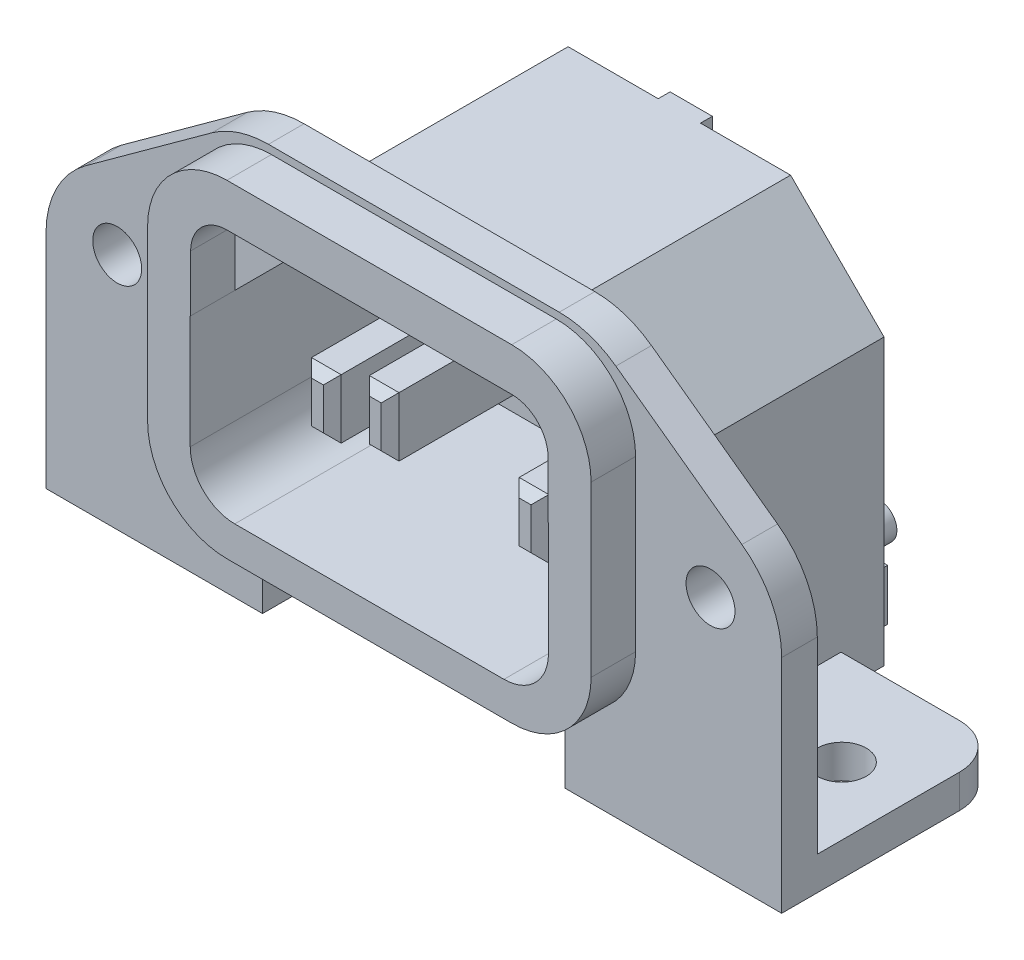
SolidWorks part; units mm, degrees
ref_plane "Front Plane" through (0, 0, 0) normal (0, 0, 1) x (1, 0, 0)
ref_plane "Top Plane" through (0, 0, 0) normal (0, 1, 0) x (1, 0, 0)
ref_plane "Right Plane" through (0, 0, 0) normal (1, 0, 0) x (0, 0, -1)
sketch "Sketch1" plane through (0, 0, 0) normal (0, 0, 1) x (1, 0, 0)
  line L0 (-22.1179, 6.3931) -> (-13.6201, 12.5605)
  line L1 (-9.8022, 13.8) -> (9.8022, 13.8)
  line L2 (-24.8, 1.1326) -> (-24.8, -13.8)
  line L3 (-24.8, -13.8) -> (-10.15, -13.8)
  line L4 (24.8, 1.1326) -> (24.8, -13.8)
  line L5 (-24.8, 13.8) -> (24.8, -13.8) construction
  line L6 (-24.8, -13.8) -> (17.5053, 9.7408) construction
  line L7 (0, 0) -> (0, 18.0303) construction
  line L8 (22.1179, 6.3931) -> (13.6201, 12.5605)
  line L9 (9.8022, 13.8) -> (24.8, 13.8) construction
  line L10 (17.5053, 9.7408) -> (24.8, 13.8) construction
  line L11 (24.8, 13.8) -> (24.8, 1.1326) construction
  line L12 (-20, 0.6) -> (-11.571, 0.6) construction
  line L13 (-21.65, 2.25) -> (-21.65, -1.1534) construction
  line L14 (-10.15, -13.8) -> (-10.15, -10.05)
  line L15 (-10.15, -10.05) -> (10.15, -10.05)
  line L16 (10.15, -10.05) -> (10.15, -13.8)
  line L17 (-10.15, -13.8) -> (10.15, -13.8) construction
  line L18 (10.15, -13.8) -> (24.8, -13.8)
  line L19 (-9.6, 13.3) -> (9.6, 13.3)
  line L20 (-9.6, 10.45) -> (9.6, 10.45) construction
  line L21 (-12.1, 7.95) -> (-12.1, -3.45) construction
  line L22 (-9.6, -5.95) -> (9.6, -5.95) construction
  line L23 (12.1, 7.95) -> (12.1, -3.45) construction
  line L24 (-12.1, 10.45) -> (12.1, -5.95) construction
  line L25 (-12.1, -5.95) -> (12.1, 10.45) construction
  line L26 (14.95, 7.95) -> (14.95, -3.45)
  line L27 (-9.6, -8.8) -> (9.6, -8.8)
  line L28 (-14.95, 7.95) -> (-14.95, -3.45)
  line L29 (-12.05, 7.95) -> (-12.05, -3.45)
  line L30 (-9.6, -5.9) -> (9.6, -5.9)
  line L31 (12.05, 7.95) -> (12.05, -3.45)
  line L32 (-9.6, 10.4) -> (9.6, 10.4)
  arc A0 (-9.8022, 13.8) -> (-13.6201, 12.5605) centre (-9.8022, 7.3) ccw
  arc A1 (-24.8, 1.1326) -> (-22.1179, 6.3931) centre (-18.3, 1.1326) cw
  arc A2 (24.8, 1.1326) -> (22.1179, 6.3931) centre (18.3, 1.1326) ccw
  arc A3 (9.8022, 13.8) -> (13.6201, 12.5605) centre (9.8022, 7.3) cw
  circle A4 centre (-20, 2.25) radius 1.65
  circle A5 centre (20, 2.25) radius 1.65
  arc A6 (-12.1, -3.45) -> (-9.6, -5.95) centre (-9.6, -3.45) ccw construction
  arc A7 (12.1, -3.45) -> (9.6, -5.95) centre (9.6, -3.45) cw construction
  arc A8 (12.1, 7.95) -> (9.6, 10.45) centre (9.6, 7.95) ccw construction
  arc A9 (-12.1, 7.95) -> (-9.6, 10.45) centre (-9.6, 7.95) cw construction
  arc A10 (14.95, 7.95) -> (9.6, 13.3) centre (9.6, 7.95) ccw
  arc A11 (14.95, -3.45) -> (9.6, -8.8) centre (9.6, -3.45) cw
  arc A12 (-14.95, -3.45) -> (-9.6, -8.8) centre (-9.6, -3.45) ccw
  arc A13 (-14.95, 7.95) -> (-9.6, 13.3) centre (-9.6, 7.95) cw
  arc A14 (-12.05, -3.45) -> (-9.6, -5.9) centre (-9.6, -3.45) ccw
  arc A15 (12.05, -3.45) -> (9.6, -5.9) centre (9.6, -3.45) cw
  arc A16 (12.05, 7.95) -> (9.6, 10.4) centre (9.6, 7.95) ccw
  arc A17 (-12.05, 7.95) -> (-9.6, 10.4) centre (-9.6, 7.95) cw
  point P0 (0, 0)
  point P32 (0, -10.05)
  point P34 (0, 2.25)
  point P39 (0, 0)
  point P40 (0, 0)
  dimension "D5" = 251.942
  dimension "D1" = 6.5
  dimension "D6" = 3.3
  dimension "D13" = 2.5
  dimension "D2" = 49.6
  dimension "D3" = 27.6
  dimension "D4" = 10.5
  dimension "D7" = 14.4
  dimension "D8" = 3.15
  dimension "D9" = 3.75
  dimension "D10" = 20.3
  dimension "D11" = 16.4
  dimension "D12" = 24.2
  dimension "D14" = 2.85
  dimension "D15" = 0.05
extrude "Boss-Extrude1" add sketch "Sketch1" along normal blind 2.4 contours A3 L1 A0 L0 A1 L2 L3 L14 L15 L16 L18 L4 A2 L8 A5 A4 L28 A13 L19 A10 L26 A11 L27 A12 | A13 L28 A12 L27 A11 L26 A10 L19 L21 A9 L20 A8 L23 A7 L22 A6 region at (-17.5356, 9.0174, 0) region at (0, 12.9282, 0)
extrude "Boss-Extrude2" add sketch "Sketch1<3>" along normal blind 3 from surface contours A13 L28 A12 L27 A11 L26 A10 L19 L21 A9 L20 A8 L23 A7 L22 A6 region at (0, 12.9282, 0) starting at face at (21.65, 2.25, 2.4)
sketch "Sketch1<3>" plane through (0, 0, 0) normal (0, 0, 1) x (1, 0, 0) same geometry as "Sketch1"
sketch "Sketch2" plane through (0, 0, 0) normal (0, 0, -1) x (-1, 0, 0)
  line L0 (24.8, -13.8) -> (10.15, -13.8) construction
  line L1 (-7.5, 11.7) -> (7.5, 11.7)
  line L2 (-13.8, 5.4) -> (-13.8, -13.8)
  line L3 (-13.8, -13.8) -> (13.8, -13.8)
  line L4 (13.8, 5.4) -> (13.8, -13.8)
  line L5 (-10.5254, 8.6746) -> (13.8, -13.8) construction
  line L6 (-13.8, -13.8) -> (10.5254, 8.6746) construction
  line L7 (-13.8, 5.4) -> (-7.5, 11.7)
  line L8 (7.5, 11.7) -> (13.8, 5.4)
  line L9 (0, -1.05) -> (0, 19.8116) construction
  line L10 (-13.8, 11.7) -> (-7.5, 11.7) construction
  line L11 (-13.8, 11.7) -> (-10.5254, 8.6746) construction
  line L12 (-13.8, 11.7) -> (-13.8, 5.4) construction
  line L13 (7.5, 11.7) -> (13.8, 11.7) construction
  line L14 (10.5254, 8.6746) -> (13.8, 11.7) construction
  line L15 (13.8, 11.7) -> (13.8, 5.4) construction
  point P0 (0, -1.05)
  point P14 (0, 0)
  dimension "D1" = 25.5
  dimension "D2" = 15
  dimension "D3" = 6.3
  dimension "D4" = 90
extrude "Boss-Extrude3" add sketch "Sketch2" along normal blind 15.5 and the other way offset from surface 3 other way up to face at (0, 2.25, 5.4)
sketch "Sketch3" plane through (0, 0, 2.4) normal (0, 0, 1) x (1, 0, 0)
  line L0 (-12.05, 7.15) -> (-8.8, 10.4)
  line L1 (0, 0) -> (0, 16.9382) construction
  line L2 (12.05, 7.15) -> (8.8, 10.4)
  arc A1 (-12.05, 7.15) -> (-8.8, 10.4) centre (-9.7647, 8.1147) cw
  arc A2 (12.05, 7.15) -> (8.8, 10.4) centre (9.7647, 8.1147) ccw
  point P11 (0, 0)
  point P12 (0, 0)
  point P13 (-8.8, 10.4)
  point P15 (0, 0)
  point P16 (-12.05, 7.15)
sketch "Sketch4" plane through (0, 0, -15.5) normal (0, 0, -1) x (-1, 0, 0)
  line L0 (12.075, -3.5) -> (12.075, 4.131)
  line L1 (12.075, 4.131) -> (6.206, 10)
  line L2 (6.206, 10) -> (-6.206, 10)
  line L3 (-6.206, 10) -> (-12.075, 4.131)
  line L4 (-12.075, 4.131) -> (-12.075, -3.5)
  line L5 (-9.075, -6.5) -> (9.075, -6.5)
  line L6 (13.8, -13.8) -> (13.8, 5.4)
  line L7 (13.8, 5.4) -> (7.5, 11.7)
  line L8 (7.5, 11.7) -> (-7.5, 11.7)
  line L9 (-7.5, 11.7) -> (-13.8, 5.4)
  line L10 (-13.8, 5.4) -> (-13.8, -13.8)
  line L11 (-13.8, -13.8) -> (13.8, -13.8)
  line L12 (13.8, -13.8) -> (13.8, 5.4) construction
  line L13 (13.8, 5.4) -> (7.5, 11.7) construction
  line L14 (7.5, 11.7) -> (-7.5, 11.7) construction
  line L15 (-7.5, 11.7) -> (-13.8, 5.4) construction
  line L16 (-13.8, 5.4) -> (-13.8, -13.8) construction
  line L17 (-13.8, -13.8) -> (13.8, -13.8) construction
  line L19 (0, 0) -> (0, 16.9382) construction
  arc A0 (12.075, -3.5) -> (9.075, -6.5) centre (9.075, -3.5) cw
  arc A1 (-9.075, -6.5) -> (-12.075, -3.5) centre (-9.075, -3.5) cw
  dimension "D6" = 3
  dimension "D3" = 24.15
  dimension "D2" = 16.5
  dimension "D4" = 8.3
  dimension "D5" = 270
  dimension "D1" = 0
extrude "Cut-Extrude1" cut sketch "Sketch4" against normal blind 25.5 from offset 5 offset against normal yes
extrude "Boss-Extrude4" add sketch "Sketch3" against normal up to surface (2.4 mm away) up to face at (21.65, 2.25, 0)
sketch "Sketch6" plane through (0, -13.8, 0) normal (0, -1, 0) x (1, 0, 0)
  line L0 (-24.8, 0) -> (-24.8, -9.6)
  line L1 (-21.8, -12.6) -> (-13.8, -12.6)
  line L2 (-13.8, 0) -> (-13.8, -15.5) construction
  line L3 (-24.8, 2.4) -> (24.8, 2.4) construction
  line L4 (-24.8, 0) -> (-13.8, 0)
  line L5 (-13.8, 0) -> (-13.8, -12.6)
  line L6 (-21.9, -6.2) -> (-21.9, -4.6864) construction
  line L7 (-20.25, -7.85) -> (-18.4114, -7.85) construction
  line L8 (0, 0) -> (0, -9.1869) construction
  line L9 (24.8, 0) -> (13.8, 0)
  line L10 (24.8, 0) -> (24.8, -9.6)
  line L11 (21.8, -12.6) -> (13.8, -12.6)
  line L12 (13.8, 0) -> (13.8, -12.6)
  arc A0 (-24.8, -9.6) -> (-21.8, -12.6) centre (-21.8, -9.6) ccw
  circle A1 centre (-20.25, -6.2) radius 1.65
  circle A2 centre (20.25, -6.2) radius 1.65
  arc A3 (24.8, -9.6) -> (21.8, -12.6) centre (21.8, -9.6) cw
  dimension "D1" = 15
  dimension "D2" = 3
  dimension "D3" = 2.9
  dimension "D5" = 3.3
  dimension "D4" = 4.75
extrude "Boss-Extrude5" add sketch "Sketch6" against normal blind 2.25
sketch "Sketch7" plane through (0, 0, 2.4) normal (0, 0, 1) x (1, 0, 0)
  line L0 (-10.2, -13.8) -> (-10.2, -9.8)
  line L1 (-24.8, -13.8) -> (24.8, -13.8) construction
  line L2 (-10.2, -9.8) -> (10.2, -9.8)
  line L3 (10.2, -9.8) -> (10.2, -13.8)
  line L4 (0, 0) -> (0, -4.0727) construction
  line L5 (-10.2, -13.8) -> (10.2, -13.8)
  dimension "D1" = 4
  dimension "D2" = 20.4
extrude "Cut-Extrude2" cut sketch "Sketch7" against normal blind 16
sketch "Sketch8" plane through (0, 0, -15.5) normal (0, 0, -1) x (-1, 0, 0)
  line L0 (0, 16.86) -> (0, -19.181) construction
  line L1 (-1.425, 11.7) -> (-1.425, 6.3)
  line L2 (-7.5, 11.7) -> (7.5, 11.7) construction
  line L3 (-2.6476, 3.3324) -> (-1.3, -2.2)
  line L4 (-1.3, -2.2) -> (-1.3, -10.1)
  line L5 (-13.8, -13.8) -> (13.8, -13.8) construction
  line L6 (-1.3, -10.1) -> (-0.65, -14.85)
  line L7 (-0.65, -14.85) -> (-0.65, -17.85)
  line L8 (-2.725, 3.9773) -> (2.725, 3.9773) construction
  line L9 (-0.65, -17.85) -> (0.65, -17.85)
  line L10 (-1.425, 11.7) -> (1.425, 11.7)
  line L11 (7.5, 11.7) -> (-7.5, 11.7) construction
  line L12 (0.65, -14.85) -> (0.65, -17.85)
  line L13 (-0.75, 10.2) -> (0.75, 10.2)
  line L14 (-0.75, 10.2) -> (-0.75, 7.2)
  line L15 (-0.75, 7.2) -> (0.75, 7.2)
  line L16 (0.75, 10.2) -> (0.75, 7.2)
  line L17 (-0.75, 10.2) -> (0.75, 7.2) construction
  line L18 (-0.75, 7.2) -> (0.75, 10.2) construction
  line L19 (1.3, -10.1) -> (0.65, -14.85)
  line L20 (1.3, -2.2) -> (1.3, -10.1)
  line L21 (2.6476, 3.3324) -> (1.3, -2.2)
  line L22 (1.425, 11.7) -> (1.425, 6.3)
  line L23 (-13.8, -11.55) -> (-13.8, 5.4) construction
  line L24 (4.447, -1.1452) -> (6.9, -4.55)
  line L25 (9.7, 0.55) -> (9.7, -4.55)
  line L26 (6.8, 3.45) -> (12.1154, 3.45) construction
  line L27 (6.9, -4.55) -> (6.9, -9.55)
  line L28 (9.7, -4.55) -> (9.7, -9.55)
  line L29 (6.9, -9.55) -> (8.4, -12.35)
  line L30 (8.4, -12.35) -> (8.4, -17.85)
  line L31 (9.7, -9.55) -> (9.7, -12.35)
  line L32 (9.7, -12.35) -> (9.7, -17.85)
  line L33 (8.4, -17.85) -> (9.7, -17.85)
  line L34 (-9.7, 0.55) -> (-9.7, -4.55)
  line L35 (-9.7, -4.55) -> (-9.7, -9.55)
  line L36 (-9.7, -9.55) -> (-9.7, -12.35)
  line L37 (-9.7, -12.35) -> (-9.7, -17.85)
  line L38 (-8.4, -17.85) -> (-9.7, -17.85)
  line L39 (-8.4, -12.35) -> (-8.4, -17.85)
  line L40 (-6.9, -9.55) -> (-8.4, -12.35)
  line L41 (-6.9, -4.55) -> (-6.9, -9.55)
  line L42 (-4.447, -1.1452) -> (-6.9, -4.55)
  arc A0 (-1.425, 6.3) -> (-2.6476, 3.3324) centre (0, 3.9773) ccw
  circle A1 centre (0, 3.9773) radius 1.25
  arc A2 (1.425, 6.3) -> (2.6476, 3.3324) centre (0, 3.9773) cw
  circle A3 centre (-6.8, 0.55) radius 1.25
  circle A4 centre (6.8, 0.55) radius 1.25
  arc A5 (9.7, 0.55) -> (4.447, -1.1452) centre (6.8, 0.55) ccw
  circle A6 centre (-6.8, 0.55) radius 2.9 construction
  arc A7 (4.447, -1.1452) -> (9.7, 0.55) centre (6.8, 0.55) ccw construction
  arc A8 (-9.7, 0.55) -> (-4.447, -1.1452) centre (-6.8, 0.55) cw
  point P19 (0, 8.7)
  point P28 (0, -17.85)
  point P34 (0, 11.7)
  dimension "D1" = 2.85
  dimension "D9" = 2.5
  dimension "D16" = 13.6
  dimension "D18" = 2.5
  dimension "D19" = 5.8
  dimension "D2" = 5.45
  dimension "D3" = 8.5
  dimension "D4" = 5.4
  dimension "D5" = 2.6
  dimension "D6" = 3.7
  dimension "D7" = 29.55
  dimension "D8" = 3
  dimension "D10" = 3
  dimension "D11" = 1.5
  dimension "D12" = 1.5
  dimension "D13" = 1.3
  dimension "D14" = 7.7227
  dimension "D15" = 13.8
  dimension "D17" = 11.15
  dimension "D20" = 8
  dimension "D21" = 2.8
  dimension "D22" = 5
  dimension "D23" = 2.8
  dimension "D24" = 1.3
extrude "Boss-Extrude6" add sketch "Sketch8" along normal blind 0.8
sketch "Sketch9" plane through (0, 0, -15.5) normal (0, 0, -1) x (-1, 0, 0)
  line L0 (-4.9768, 5.9229) -> (-2.9179, -2.5299)
  line L1 (-2.9179, -2.5299) -> (-2.9179, -7.6)
  line L2 (-8.4, -13.8) -> (-0.7937, -13.8) construction
  line L3 (-2.9179, -13.8) -> (-1.4179, -13.8)
  line L4 (-1.4179, -13.8) -> (-1.4179, -8.4)
  line L5 (-1.4179, -2.3499) -> (-3.5195, 6.2779)
  line L6 (-3.5195, 6.2779) -> (-4.9768, 5.9229)
  line L7 (-2.6476, 3.3324) -> (-1.3, -2.2) construction
  line L8 (0, 0) -> (0, 3.9773) construction
  line L9 (1.4179, -2.3499) -> (3.5195, 6.2779)
  line L10 (1.4179, -13.8) -> (1.4179, -8.4)
  line L11 (2.9179, -13.8) -> (1.4179, -13.8)
  line L12 (2.9179, -2.5299) -> (2.9179, -7.6)
  line L13 (4.9768, 5.9229) -> (2.9179, -2.5299)
  line L14 (3.5195, 6.2779) -> (4.9768, 5.9229)
  line L15 (0.7937, -13.8) -> (8.4, -13.8) construction
  line L16 (1.4179, -4.4057) -> (2.9179, -4.4057) construction
  line L18 (1.4179, -8.4) -> (1.4179, -7.6) construction
  line L19 (1.4179, -7.6) -> (1.4179, -2.3499)
  line L20 (2.9179, -7.6) -> (2.9179, -8.4) construction
  line L21 (2.9179, -8.4) -> (2.9179, -13.8)
  line L22 (-1.4179, -8.4) -> (-1.4179, -7.6) construction
  line L23 (-1.4179, -7.6) -> (-1.4179, -2.3499)
  line L24 (-2.9179, -7.6) -> (-2.9179, -8.4) construction
  line L25 (-2.9179, -8.4) -> (-2.9179, -13.8)
  line L28 (9.7, -17.85) -> (9.7, 0.55) construction
  line L30 (9.7, -13.8) -> (11.5, -13.8)
  line L31 (9.7, -13.8) -> (13.8, -13.8) construction
  line L32 (11.5, -13.8) -> (11.5, -10.35)
  line L33 (11.5, -10.35) -> (9.7, -10.35)
  line L34 (9.7, -10.35) -> (9.7, -13.8)
  line L35 (-11.5, -10.35) -> (-9.7, -10.35)
  line L36 (-11.5, -13.8) -> (-11.5, -10.35)
  line L37 (-9.7, -13.8) -> (-11.5, -13.8)
  line L38 (-9.7, -10.35) -> (-9.7, -13.8)
  arc A0 (2.9179, -8.4) -> (2.9179, -7.6) centre (2.1679, -8) ccw
  arc A1 (1.4179, -8.4) -> (2.9179, -8.4) centre (2.1679, -8) ccw construction
  arc A2 (2.9179, -7.6) -> (1.4179, -7.6) centre (2.1679, -8) ccw construction
  arc A3 (1.4179, -7.6) -> (1.4179, -8.4) centre (2.1679, -8) ccw
  arc A4 (-2.9179, -8.4) -> (-2.9179, -7.6) centre (-2.1679, -8) cw
  arc A5 (-1.4179, -7.6) -> (-1.4179, -8.4) centre (-2.1679, -8) cw
  circle A6 centre (5.675, -8) radius 1.2
  circle A7 centre (10.925, -8) radius 1.2
  circle A8 centre (-10.925, -8) radius 1.2
  circle A9 centre (-5.675, -8) radius 1.2
  point P46 (2.1679, -4.4057)
  dimension "D6" = 5.8
  dimension "D7" = 0.85
  dimension "D8" = 2.4
  dimension "D12" = 2.4
  dimension "D1" = 0.15
  dimension "D2" = 1.5
  dimension "D3" = 1.5
  dimension "D4" = 11.4501
  dimension "D5" = 8.7
  dimension "D9" = 1.8
  dimension "D10" = 3.45
  dimension "D11" = 5.675
  dimension "D13" = 5.25
extrude "Boss-Extrude10" add sketch "Sketch9" along normal blind 2.54
sketch "Sketch10" plane through (0, 0, -13.6) normal (0, 0, 1) x (1, 0, 0)
  line L0 (0, 0) -> (0, -20.0579) construction
  line L1 (8.6, -13.8) -> (8.6, -11.1)
  line L2 (-10.2, -13.8) -> (10.2, -13.8) construction
  line L3 (8.6, -11.1) -> (5.9, -11.1)
  line L4 (5.9, -11.1) -> (5.9, -13.8)
  line L5 (1.65, -13.8) -> (1.65, -11.1)
  line L6 (1.65, -11.1) -> (-1.65, -11.1)
  line L7 (-1.65, -11.1) -> (-1.65, -13.8)
  line L8 (10.2, -13.8) -> (10.2, -9.8) construction
  line L9 (5.9, -13.8) -> (8.6, -13.8)
  line L10 (1.65, -13.8) -> (-1.65, -13.8)
  line L11 (-5.9, -11.1) -> (-5.9, -13.8)
  line L12 (-8.6, -11.1) -> (-5.9, -11.1)
  line L13 (-8.6, -13.8) -> (-8.6, -11.1)
  line L14 (-5.9, -13.8) -> (-8.6, -13.8)
  point P11 (0, -11.1)
  dimension "D1" = 1.6
  dimension "D2" = 2.7
  dimension "D3" = 3.3
  dimension "D4" = 2.7
extrude "Cut-Extrude3" cut sketch "Sketch10" against normal up to surface (1.9 mm away) up to face at (-9.05, -15.825, -15.5)
sketch "Sketch11" plane through (0, 0, -15.5) normal (0, 0, -1) x (-1, 0, 0)
  line L0 (-12.1, -5.55) -> (-10.1973, -5.55) construction
  line L1 (0, 0) -> (0, -4.9949) construction
  line L2 (12.1, -5.55) -> (10.1973, -5.55) construction
  line L3 (-10.925, -6.8) -> (-12.9823, -6.8) construction
  line L4 (-13.8, -11.55) -> (-13.8, 5.4) construction
  circle A0 centre (-10.925, -8) radius 1.2 construction
  circle A1 centre (-10.925, -8) radius 1.2 construction
  text T0 "N" font "Century Gothic" height 2
  text T1 "L" font "Century Gothic" height 2
  dimension "D1" = 1.25
  dimension "D2" = 1.7
extrude "Boss-Extrude11" add sketch "Sketch11" along normal blind 0.1
sketch "Sketch12" plane through (0, 0, -15.5) normal (0, 0, -1) x (-1, 0, 0)
  line L0 (5.2867, 11.0846) -> (5.2867, 10.0846)
  line L1 (4.2867, 10.0846) -> (6.2867, 10.0846)
  line L2 (4.6228, 9.4846) -> (5.9505, 9.4846)
  line L3 (5.1007, 8.8846) -> (5.4726, 8.8846)
  line L4 (5.2867, 10.0846) -> (5.2867, 9.4846) construction
  line L5 (5.2867, 8.8846) -> (5.2867, 7.5846) construction
  line L6 (5.2867, 9.4846) -> (5.2867, 8.8846) construction
  point P4 (5.2867, 10.0846)
  point P12 (5.2867, 8.8846)
  point P13 (5.2867, 9.4846)
  dimension "D1" = 3.5
  dimension "D2" = 2
  dimension "D3" = 1
  dimension "D4" = 0.6
  dimension "D5" = 0.6
extrude "Extrude-Thin1" add sketch "Sketch12" along normal blind 0.1 thin thin type mid plane wall 0.25
sketch "Sketch13" plane through (0, 0, -10.5) normal (0, 0, 1) x (1, 0, 0)
  line L0 (0, 10) -> (0, -6.5) construction
  line L1 (9.075, -6.5) -> (-9.075, -6.5) construction
  line L6 (-6.206, 10) -> (6.206, 10) construction
  line L7 (8, -2.3) -> (6, -2.3)
  line L12 (-1, 5.7) -> (1, 5.7)
  line L13 (-1, 5.7) -> (-1, 1.7)
  line L14 (-1, 1.7) -> (1, 1.7)
  line L15 (1, 5.7) -> (1, 1.7)
  line L16 (-1, 5.7) -> (1, 1.7) construction
  line L17 (-1, 1.7) -> (1, 5.7) construction
  line L18 (-8, 1.7) -> (-6, 1.7)
  line L19 (-8, 1.7) -> (-8, -2.3)
  line L20 (-8, -2.3) -> (-6, -2.3)
  line L21 (-6, 1.7) -> (-6, -2.3)
  line L22 (-8, 1.7) -> (-6, -2.3) construction
  line L23 (-8, -2.3) -> (-6, 1.7) construction
  line L24 (6, 1.7) -> (6, -2.3)
  line L25 (8, 1.7) -> (8, -2.3)
  line L26 (8, 1.7) -> (6, 1.7)
  point P3 (0, 3.7)
  point P12 (-7, -0.3)
  dimension "D1" = 4
  dimension "D2" = 2
  dimension "D3" = 4.3
  dimension "D4" = 4
  dimension "D5" = 2
  dimension "D6" = 12
extrude "Boss-Extrude12" add sketch "Sketch13" along normal blind 15.5 contours L15 L12 L13 L14 region at (0, 3.7, -10.5)
extrude "Boss-Extrude13" add sketch "Sketch13<3>" along normal blind 12.4 contours L21 L18 L19 L20 | L25 L26 L24 L7 region at (7, -0.3, -10.5) region at (-7, -0.3, -10.5)
sketch "Sketch13<3>" plane through (0, 0, -10.5) normal (0, 0, 1) x (1, 0, 0) same geometry as "Sketch13"
chamfer "Chamfer1" distance 0.6 angle 45 12 edges at (7, 1.7, 1.9) (8, -0.3, 1.9) (7, -2.3, 1.9) (6, -0.3, 1.9) (-7, -2.3, 1.9) (-6, -0.3, 1.9) (-7, 1.7, 1.9) (-8, -0.3, 1.9) (0, 5.7, 5) (-1, 3.7, 5) (0, 1.7, 5) (1, 3.7, 5)
